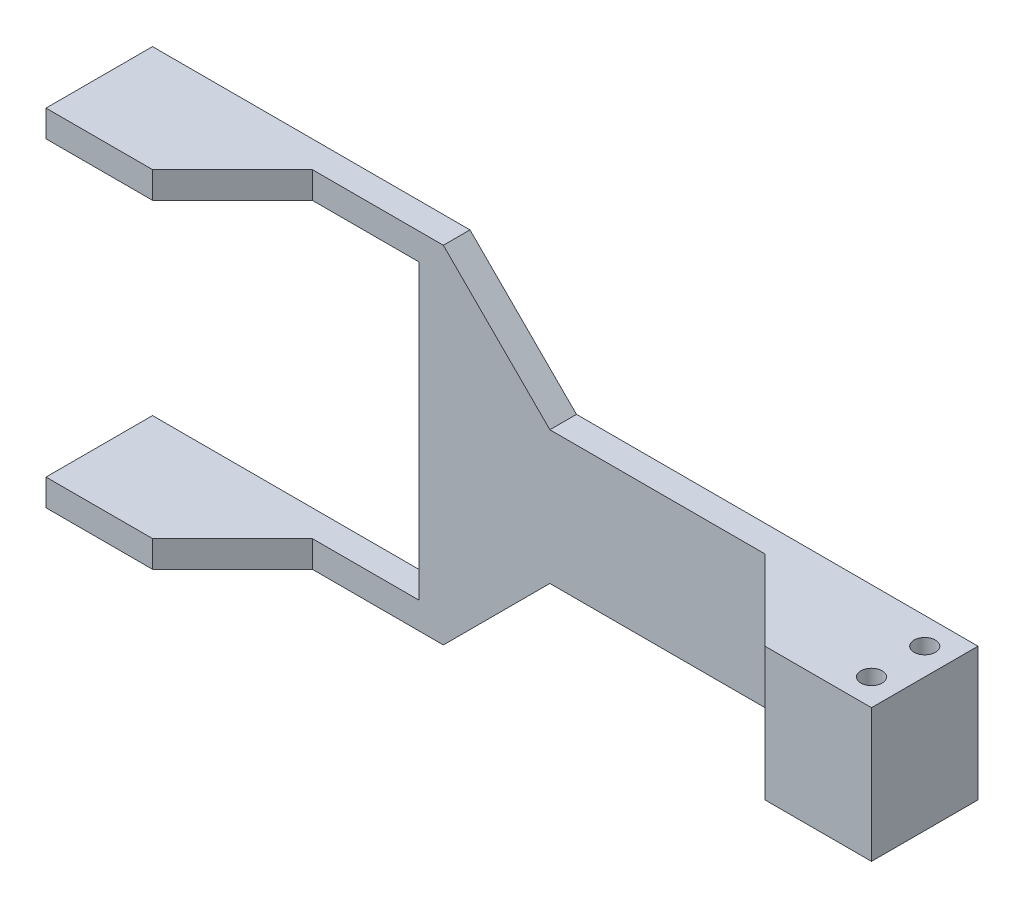
SolidWorks part; units mm, degrees
ref_plane "Plan de face" through (0, 0, 0) normal (0, 0, 1) x (1, 0, 0)
ref_plane "Plan de dessus" through (0, 0, 0) normal (0, 1, 0) x (1, 0, 0)
ref_plane "Plan de droite" through (0, 0, 0) normal (1, 0, 0) x (0, 0, -1)
sketch "Esquisse1" plane through (0, 0, 0) normal (0, 0, 1) x (1, 0, 0)
  line L0 (-55, 32.5) -> (-55, 27.5)
  line L1 (-55, 27.5) -> (0, 27.5)
  line L2 (0, 27.5) -> (0, -27.5)
  line L3 (4.61, -32.5) -> (-55, -32.5)
  line L4 (100, -12.5) -> (100, 12.5)
  line L5 (100, 12.5) -> (24.61, 12.5)
  line L6 (24.61, 12.5) -> (4.61, 32.5)
  line L7 (4.61, 32.5) -> (-55, 32.5)
  line L8 (-163.0775, 0) -> (196.6083, 0) construction
  line L9 (198.9296, 0) -> (-198.9296, 0) construction
  line L10 (24.61, -12.5) -> (4.61, -32.5)
  line L11 (100, -12.5) -> (24.61, -12.5)
  line L12 (-55, -27.5) -> (0, -27.5)
  line L13 (-55, -32.5) -> (-55, -27.5)
  point P17 (100, 0)
  point P18 (0, 0)
  dimension "D1" = 55
  dimension "D2" = 5
  dimension "D3" = 25
  dimension "D4" = 55
  dimension "D5" = 135
  dimension "D6" = 100
extrude "Extrusion1" add sketch "Esquisse1" along normal blind 20
sketch "Esquisse2" plane through (0, -12.5, 0) normal (0, -1, 0) x (1, 0, 0)
  line L0 (-77.7842, 10) -> (135.6408, 10) construction
  line L1 (24.61, 20) -> (100, 20) construction
  line L2 (24.61, 0) -> (100, 0) construction
  line L3 (100, 20) -> (100, 0) construction
  circle A0 centre (95, 15) radius 2
  circle A1 centre (95, 5) radius 2
  dimension "D3" = 4
  dimension "D1" = 5
  dimension "D2" = 10
extrude "Enlèv. mat.-Extru.1" cut sketch "Esquisse2" against normal through all
sketch "Esquisse3" plane through (0, -32.5, 0) normal (0, -1, 0) x (1, 0, 0)
  line L0 (-35, 20) -> (-20, 5)
  line L1 (-20, 5) -> (65, 5)
  line L2 (65, 5) -> (80, 20)
  line L3 (80, 20) -> (-35, 20)
  line L4 (-55, 20) -> (4.61, 20) construction
  line L5 (24.61, 0) -> (100, 0) construction
  dimension "D1" = 20
  dimension "D2" = 20
  dimension "D3" = 5
  dimension "D4" = 45
  dimension "D5" = 45
extrude "Enlèv. mat.-Extru.2" cut sketch "Esquisse3" against normal through all
